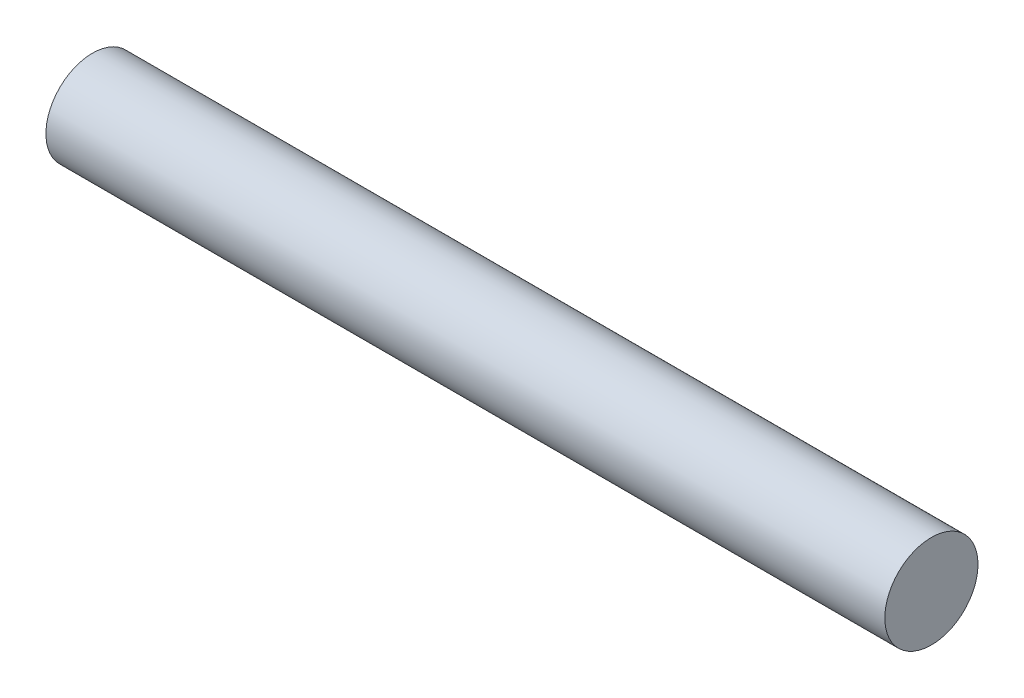
SolidWorks part; units mm, degrees
ref_plane "Front Plane" through (0, 0, 0) normal (0, 0, 1) x (1, 0, 0)
ref_plane "Top Plane" through (0, 0, 0) normal (0, 1, 0) x (1, 0, 0)
ref_plane "Right Plane" through (0, 0, 0) normal (1, 0, 0) x (0, 0, -1)
sketch "Sketch2" plane through (0, 0, 0) normal (1, 0, 0) x (0, 0, -1)
  circle A0 centre (0, 0) radius 6.35
extrude "Boss-Extrude1" add sketch "Sketch2" along normal blind 114.3
ref_plane "Plane1" through (0, 6.985, 0) normal (0, 1, 0) x (1, 0, 0)
sketch "Sketch3" plane through (0, 6.985, 0) normal (0, 1, 0) x (1, 0, 0)
  line L0 (52.324, 0) -> (77.724, 0)
  line L3 (114.3, 0) -> (0, 0) construction
  line L4 (26.924, 0) -> (52.324, 0)
